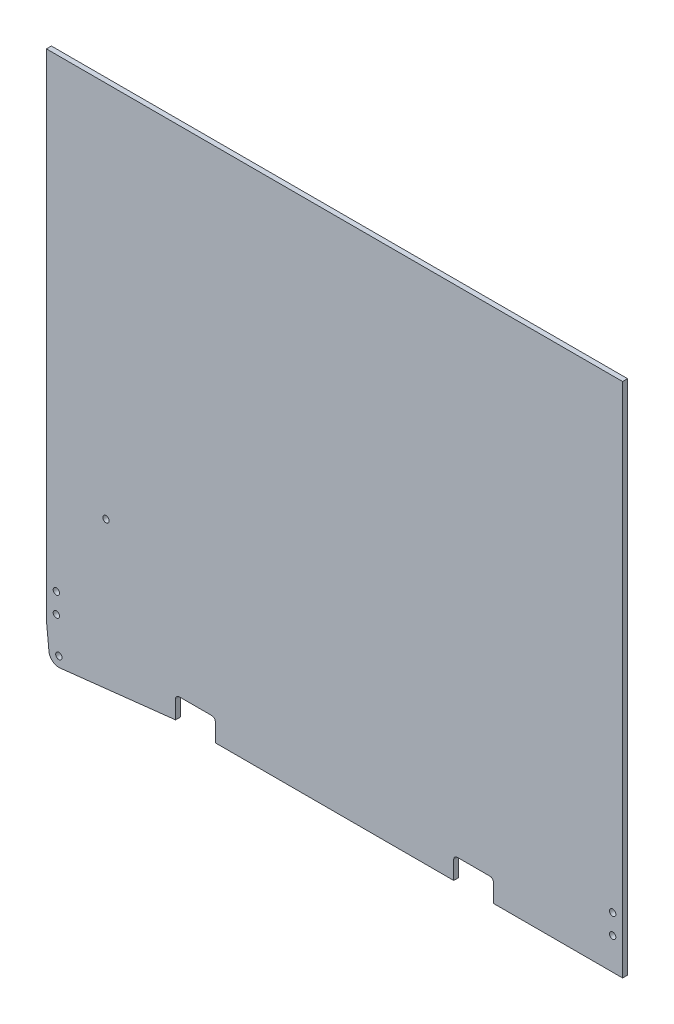
SolidWorks part; units mm, degrees
ref_plane "Front Plane" through (0, 0, 0) normal (0, 0, 1) x (1, 0, 0)
ref_plane "Top Plane" through (0, 0, 0) normal (0, 1, 0) x (1, 0, 0)
ref_plane "Right Plane" through (0, 0, 0) normal (1, 0, 0) x (0, 0, -1)
sketch "Sketch1" plane through (0, 0, 0) normal (0, 0, 1) x (1, 0, 0)
  line L0 (82.55, -20.32) -> (82.55, -6.35)
  line L2 (0, 0) -> (0, 309.88)
  line L3 (0, 309.88) -> (368.3, 309.88)
  line L4 (368.3, -20.32) -> (368.3, 309.88)
  line L5 (82.55, -6.35) -> (107.95, -6.35)
  line L6 (107.95, -6.35) -> (107.95, -20.32)
  line L7 (107.95, -20.32) -> (260.35, -20.32)
  line L8 (260.35, -20.32) -> (260.35, -6.35)
  line L9 (260.35, -6.35) -> (285.75, -6.35)
  line L10 (285.75, -6.35) -> (285.75, -20.32)
  line L11 (285.75, -20.32) -> (368.3, -20.32)
  line L12 (361.95, 12.7) -> (368.3, 12.7) construction
  line L13 (0, 0) -> (6.35, 0) construction
  line L14 (0.0315, -6.9818) -> (1.619, -22.8568)
  line L15 (8.6391, -28.5361) -> (82.55, -20.32)
  line L16 (0, 0) -> (0, -6.35)
  circle A0 centre (6.35, 0) radius 2.032
  circle A1 centre (6.35, 12.7) radius 2.032
  circle A2 centre (361.95, 0) radius 2.032
  circle A3 centre (361.95, 12.7) radius 2.032
  arc A5 (1.619, -22.8568) -> (8.6391, -28.5361) centre (7.9375, -22.225) ccw
  circle A6 centre (7.9375, -22.225) radius 2.032
  arc A7 (0, -6.35) -> (0.0315, -6.9818) centre (6.35, -6.35) ccw
  circle A8 centre (38.1, 68.58) radius 2.032
  dimension "D6" = 4.064
  dimension "D10" = 6.35
  dimension "D11" = 4.064
  dimension "D17" = 38.1
  dimension "D2" = 330.2
  dimension "D3" = 13.97
  dimension "D4" = 25.4
  dimension "D5" = 152.4
  dimension "D7" = 12.7
  dimension "D8" = 6.35
  dimension "D9" = 20.32
  dimension "D12" = 22.225
  dimension "D13" = 1.5875
  dimension "D14" = 82.55
  dimension "D15" = 368.3
  dimension "D16" = 6.35
  dimension "D18" = 88.9
extrude "Boss-Extrude1" add sketch "Sketch1" along normal blind 3.175
fillet "Fillet1" radius 2.286 4 edges at (285.75, -6.35, 1.5875) (107.95, -6.35, 1.5875) (260.35, -6.35, 1.5875) (82.55, -6.35, 1.5875)
